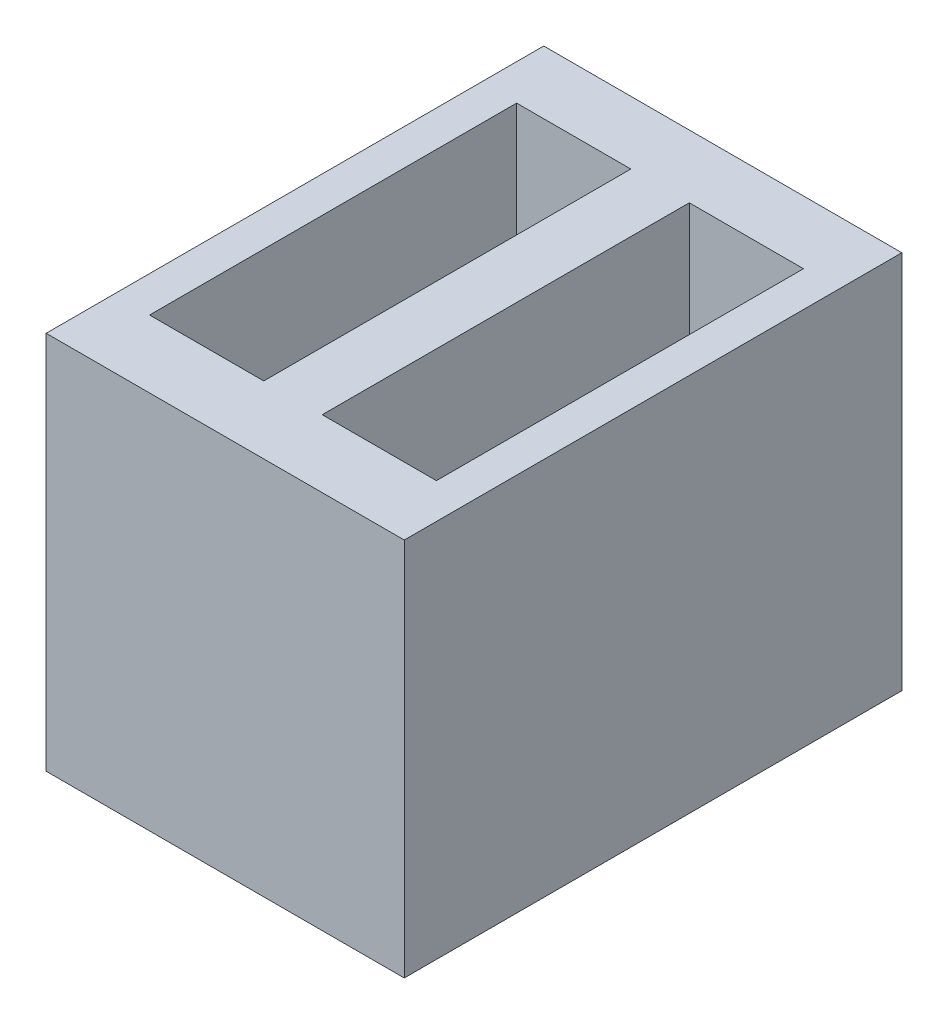
SolidWorks part; units mm, degrees
material "AISI 1020 Steel, Cold Rolled"
ref_plane "Alzado" through (0, 0, 0) normal (0, 0, 1) x (1, 0, 0)
ref_plane "Planta" through (0, 0, 0) normal (0, 1, 0) x (1, 0, 0)
ref_plane "Vista lateral" through (0, 0, 0) normal (1, 0, 0) x (0, 0, -1)
sketch "Croquis1" plane through (0, 0, 0) normal (0, 1, 0) x (1, 0, 0)
  line L1 (0, 0) -> (4.39, 0)
  line L2 (0, 0) -> (0, 6.1)
  line L3 (0, 6.1) -> (4.39, 6.1)
  line L4 (4.39, 0) -> (4.39, 6.1)
  dimension "D1" = 6.1
  dimension "D2" = 4.39
extrude "Saliente-Extruir1" add sketch "Croquis1" along normal blind 4.65
sketch "Croquis3" plane through (0, 4.65, 0) normal (0, 1, 0) x (1, 0, 0)
  line L0 (2.195, 0) -> (2.195, 3.0776) construction
  line L1 (0, 0) -> (4.39, 0) construction
  line L2 (2.195, 3.0776) -> (1.14, 3.0776) construction
  line L3 (2.195, 3.0776) -> (3.2568, 3.0776) construction
  line L5 (1.84, 0.8276) -> (0.44, 0.8276)
  line L6 (1.84, 0.8276) -> (1.84, 5.3276)
  line L7 (1.84, 5.3276) -> (0.44, 5.3276)
  line L8 (0.44, 0.8276) -> (0.44, 5.3276)
  line L9 (1.84, 0.8276) -> (0.44, 5.3276) construction
  line L10 (1.84, 5.3276) -> (0.44, 0.8276) construction
  line L11 (2.5568, 0.8276) -> (3.9568, 0.8276)
  line L12 (2.5568, 0.8276) -> (2.5568, 5.3276)
  line L13 (2.5568, 5.3276) -> (3.9568, 5.3276)
  line L14 (3.9568, 0.8276) -> (3.9568, 5.3276)
  line L15 (2.5568, 0.8276) -> (3.9568, 5.3276) construction
  line L16 (2.5568, 5.3276) -> (3.9568, 0.8276) construction
  line L17 (4.39, 0) -> (4.39, 6.1) construction
  dimension "D1" = 4.5
  dimension "D2" = 1.4
  dimension "D3" = 0.4332
  dimension "D4" = 0.7168
  dimension "D5" = 0.8276
extrude "Cortar-Extruir1" cut sketch "Croquis3" against normal through all
